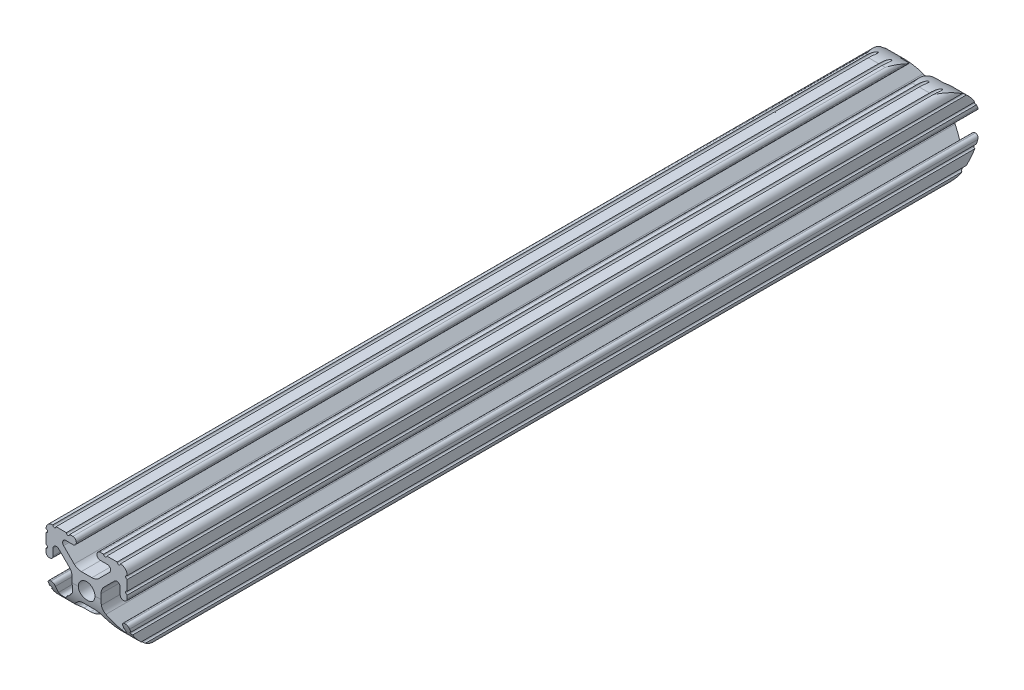
SolidWorks part; units mm, degrees
material "6061 Alloy"
ref_plane "Front Plane" through (0, 0, 0) normal (0, 0, 1) x (1, 0, 0)
ref_plane "Top Plane" through (0, 0, 0) normal (0, 1, 0) x (1, 0, 0)
ref_plane "Right Plane" through (0, 0, 0) normal (1, 0, 0) x (0, 0, -1)
sketch "Sketch1" plane through (0, 0, 0) normal (0, 0, 1) x (1, 0, 0)
  line L88 (-7.1797, -8.6452) -> (-3.9523, -5.4237)
  line L89 (-1.7093, -4.4958) -> (1.7093, -4.4958)
  line L90 (3.9523, -5.4237) -> (7.1797, -8.6452)
  line L91 (6.4164, -10.4902) -> (4.2875, -10.4902)
  line L92 (3.2385, -11.5392) -> (3.2385, -11.651)
  line L93 (4.2875, -12.7) -> (5.3171, -12.7)
  line L94 (6.3331, -12.7) -> (9.5504, -12.7)
  line L95 (12.7, -9.5504) -> (12.7, -6.3331)
  line L96 (12.7, -5.3171) -> (12.7, -4.2875)
  line L97 (11.651, -3.2385) -> (11.5392, -3.2385)
  line L98 (10.4902, -4.2875) -> (10.4902, -6.4021)
  line L99 (8.7371, -7.1294) -> (5.441, -3.8408)
  line L100 (4.5085, -1.5932) -> (4.5085, 1.5932)
  line L101 (5.441, 3.8408) -> (8.7371, 7.1294)
  line L102 (10.4902, 6.4021) -> (10.4902, 4.2875)
  line L103 (11.5392, 3.2385) -> (11.651, 3.2385)
  line L104 (12.7, 4.2875) -> (12.7, 5.3171)
  line L105 (12.7, 6.3331) -> (12.7, 9.5504)
  line L106 (9.5504, 12.7) -> (6.3331, 12.7)
  line L107 (5.3171, 12.7) -> (4.2875, 12.7)
  line L108 (3.2385, 11.651) -> (3.2385, 11.5392)
  line L109 (4.2875, 10.4902) -> (6.4768, 10.4902)
  line L110 (7.207, 8.7244) -> (3.8983, 5.4232)
  line L111 (1.6558, 4.4958) -> (-1.6558, 4.4958)
  line L112 (-3.8983, 5.4232) -> (-7.207, 8.7244)
  line L113 (-6.4768, 10.4902) -> (-4.2875, 10.4902)
  line L114 (-3.2385, 11.5392) -> (-3.2385, 11.651)
  line L115 (-4.2875, 12.7) -> (-5.3171, 12.7)
  line L116 (-6.3331, 12.7) -> (-9.5504, 12.7)
  line L117 (-12.7, 9.5504) -> (-12.7, 6.3331)
  line L118 (-12.7, 5.3171) -> (-12.7, 4.2875)
  line L119 (-11.651, 3.2385) -> (-11.5392, 3.2385)
  line L120 (-10.4902, 4.2875) -> (-10.4902, 6.4021)
  line L121 (-8.7371, 7.1294) -> (-5.441, 3.8408)
  line L122 (-4.5085, 1.5932) -> (-4.5085, -1.5932)
  line L123 (-5.441, -3.8408) -> (-8.7371, -7.1294)
  line L124 (-10.4902, -6.4021) -> (-10.4902, -4.2875)
  line L125 (-11.5392, -3.2385) -> (-11.651, -3.2385)
  line L126 (-12.7, -4.2875) -> (-12.7, -5.3171)
  line L127 (-12.7, -6.3331) -> (-12.7, -9.5504)
  line L128 (-9.5504, -12.7) -> (-6.3331, -12.7)
  line L129 (-5.3171, -12.7) -> (-4.2875, -12.7)
  line L130 (-3.2385, -11.651) -> (-3.2385, -11.5392)
  line L131 (-4.2875, -10.4902) -> (-6.4164, -10.4902)
  circle A1 centre (0, 0) radius 2.6035
  arc A104 (-7.1797, -8.6452) -> (-6.4164, -10.4902) centre (-6.4164, -9.4098) ccw
  arc A105 (-1.7093, -4.4958) -> (-3.9523, -5.4237) centre (-1.7093, -7.6708) ccw
  arc A106 (3.9523, -5.4237) -> (1.7093, -4.4958) centre (1.7093, -7.6708) ccw
  arc A107 (6.4164, -10.4902) -> (7.1797, -8.6452) centre (6.4164, -9.4098) ccw
  arc A108 (4.2875, -10.4902) -> (3.2385, -11.5392) centre (4.2875, -11.5392) ccw
  arc A109 (3.2385, -11.651) -> (4.2875, -12.7) centre (4.2875, -11.651) ccw
  arc A110 (6.3331, -12.7) -> (5.3171, -12.7) centre (5.8251, -12.7) ccw
  arc A111 (10.5664, -12.6998) -> (9.5504, -12.7) centre (10.0584, -12.7) ccw
  arc A112 (10.5664, -12.6998) -> (12.6998, -10.5664) centre (10.5918, -10.5918) ccw
  arc A113 (12.7, -9.5504) -> (12.6998, -10.5664) centre (12.7, -10.0584) ccw
  arc A114 (12.7, -5.3171) -> (12.7, -6.3331) centre (12.7, -5.8251) ccw
  arc A115 (12.7, -4.2875) -> (11.651, -3.2385) centre (11.651, -4.2875) ccw
  arc A116 (11.5392, -3.2385) -> (10.4902, -4.2875) centre (11.5392, -4.2875) ccw
  arc A117 (8.7371, -7.1294) -> (10.4902, -6.4021) centre (9.4628, -6.4021) ccw
  arc A118 (4.5085, -1.5932) -> (5.441, -3.8408) centre (7.6835, -1.5932) ccw
  arc A119 (5.441, 3.8408) -> (4.5085, 1.5932) centre (7.6835, 1.5932) ccw
  arc A120 (10.4902, 6.4021) -> (8.7371, 7.1294) centre (9.4628, 6.4021) ccw
  arc A121 (10.4902, 4.2875) -> (11.5392, 3.2385) centre (11.5392, 4.2875) ccw
  arc A122 (11.651, 3.2385) -> (12.7, 4.2875) centre (11.651, 4.2875) ccw
  arc A123 (12.7, 6.3331) -> (12.7, 5.3171) centre (12.7, 5.8251) ccw
  arc A124 (12.6998, 10.5664) -> (12.7, 9.5504) centre (12.7, 10.0584) ccw
  arc A125 (12.6998, 10.5664) -> (10.5664, 12.6998) centre (10.5918, 10.5918) ccw
  arc A126 (9.5504, 12.7) -> (10.5664, 12.6998) centre (10.0584, 12.7) ccw
  arc A127 (5.3171, 12.7) -> (6.3331, 12.7) centre (5.8251, 12.7) ccw
  arc A128 (4.2875, 12.7) -> (3.2385, 11.651) centre (4.2875, 11.651) ccw
  arc A129 (3.2385, 11.5392) -> (4.2875, 10.4902) centre (4.2875, 11.5392) ccw
  arc A130 (7.207, 8.7244) -> (6.4768, 10.4902) centre (6.4768, 9.4563) ccw
  arc A131 (1.6558, 4.4958) -> (3.8983, 5.4232) centre (1.6558, 7.6708) ccw
  arc A132 (-3.8983, 5.4232) -> (-1.6558, 4.4958) centre (-1.6558, 7.6708) ccw
  arc A133 (-6.4768, 10.4902) -> (-7.207, 8.7244) centre (-6.4768, 9.4563) ccw
  arc A134 (-4.2875, 10.4902) -> (-3.2385, 11.5392) centre (-4.2875, 11.5392) ccw
  arc A135 (-3.2385, 11.651) -> (-4.2875, 12.7) centre (-4.2875, 11.651) ccw
  arc A136 (-6.3331, 12.7) -> (-5.3171, 12.7) centre (-5.8251, 12.7) ccw
  arc A137 (-10.5664, 12.6998) -> (-9.5504, 12.7) centre (-10.0584, 12.7) ccw
  arc A138 (-10.5664, 12.6998) -> (-12.6998, 10.5664) centre (-10.5918, 10.5918) ccw
  arc A139 (-12.7, 9.5504) -> (-12.6998, 10.5664) centre (-12.7, 10.0584) ccw
  arc A140 (-12.7, 5.3171) -> (-12.7, 6.3331) centre (-12.7, 5.8251) ccw
  arc A141 (-12.7, 4.2875) -> (-11.651, 3.2385) centre (-11.651, 4.2875) ccw
  arc A142 (-11.5392, 3.2385) -> (-10.4902, 4.2875) centre (-11.5392, 4.2875) ccw
  arc A143 (-8.7371, 7.1294) -> (-10.4902, 6.4021) centre (-9.4628, 6.4021) ccw
  arc A144 (-4.5085, 1.5932) -> (-5.441, 3.8408) centre (-7.6835, 1.5932) ccw
  arc A145 (-5.441, -3.8408) -> (-4.5085, -1.5932) centre (-7.6835, -1.5932) ccw
  arc A146 (-10.4902, -6.4021) -> (-8.7371, -7.1294) centre (-9.4628, -6.4021) ccw
  arc A147 (-10.4902, -4.2875) -> (-11.5392, -3.2385) centre (-11.5392, -4.2875) ccw
  arc A148 (-11.651, -3.2385) -> (-12.7, -4.2875) centre (-11.651, -4.2875) ccw
  arc A149 (-12.7, -6.3331) -> (-12.7, -5.3171) centre (-12.7, -5.8251) ccw
  arc A150 (-12.6998, -10.5664) -> (-12.7, -9.5504) centre (-12.7, -10.0584) ccw
  arc A151 (-12.6998, -10.5664) -> (-10.5664, -12.6998) centre (-10.5918, -10.5918) ccw
  arc A152 (-9.5504, -12.7) -> (-10.5664, -12.6998) centre (-10.0584, -12.7) ccw
  arc A153 (-5.3171, -12.7) -> (-6.3331, -12.7) centre (-5.8251, -12.7) ccw
  arc A154 (-4.2875, -12.7) -> (-3.2385, -11.651) centre (-4.2875, -11.651) ccw
  arc A155 (-3.2385, -11.5392) -> (-4.2875, -10.4902) centre (-4.2875, -11.5392) ccw
extrude "Boss-Extrude1" add sketch "Sketch1" along normal mid plane 266.7
sketch "Sketch2" plane through (4.5085, 0, 0) normal (1, 0, 0) x (0, 0, -1)
  line L0 (-133.35, -1.5932) -> (-133.35, 1.5932) construction
  line L1 (-133.35, -12.6998) -> (133.35, -12.6998) construction
  line L2 (-133.35, 0) -> (-133.35, -12.7)
  line L3 (-133.35, -12.7) -> (-120.65, -12.7)
  line L4 (-133.35, -12.7) -> (133.35, -12.7) construction
  circle A0 centre (-120.65, 0) radius 3.175
  circle A1 centre (-95.25, 0) radius 3.175
  arc A2 (-133.35, 0) -> (-120.65, -12.7) centre (-120.65, 0) ccw
  dimension "D1" = 6.35
  dimension "D2" = 12.7
  dimension "D3" = 12.6998
  dimension "D4" = 25.4
extrude "Cut-Extrude1" cut sketch "Sketch2" against normal through all both and the other way through all
sketch "Sketch3" plane through (4.5085, 0, 0) normal (1, 0, 0) x (0, 0, -1)
  line L0 (133.35, 6.3331) -> (133.35, 9.5504) construction
  line L1 (133.35, -1.5932) -> (133.35, 1.5932) construction
  line L2 (-133.35, 12.7) -> (133.35, 12.7) construction
  line L3 (120.65, 12.7) -> (133.35, 12.7)
  line L4 (133.35, 12.7) -> (133.35, -12.7)
  line L5 (133.35, -12.7) -> (120.65, -12.7)
  circle A0 centre (120.65, 0) radius 12.7 construction
  arc A1 (120.65, 12.7) -> (120.65, -12.7) centre (120.65, 0) cw
  line M2 (133.35, 1.5932) -> (-92.5037, 1.5932)
  line M4 (-92.5037, -1.5932) -> (133.35, -1.5932)
  dimension "D1" = 12.7
extrude "Cut-Extrude2" cut sketch "Sketch3" against normal through all both and the other way through all contours L3 A1 L4 M2 | A1 L5 L4 M4 region at (4.5085, 9.8766, -130.5089) region at (4.5085, -9.8766, -130.5089)
